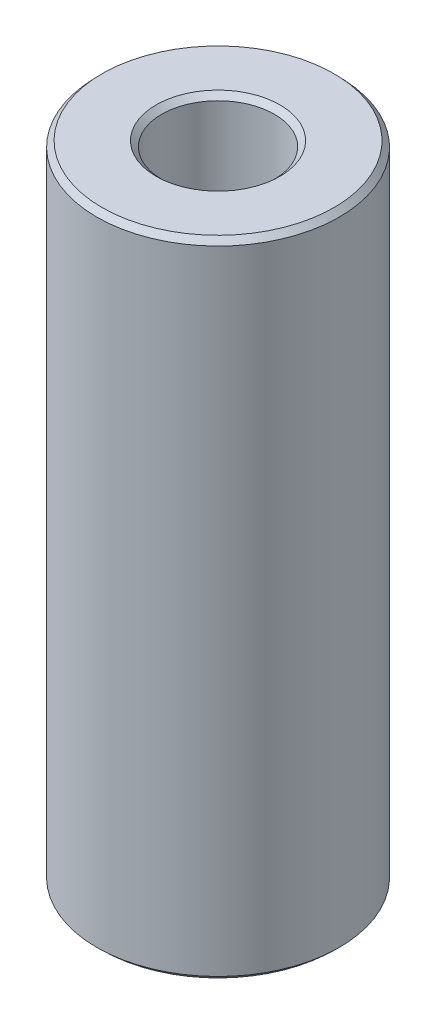
SolidWorks part; units mm, degrees
ref_plane "Front Plane" through (0, 0, 0) normal (0, 0, 1) x (1, 0, 0)
ref_plane "Top Plane" through (0, 0, 0) normal (0, 1, 0) x (1, 0, 0)
ref_plane "Right Plane" through (0, 0, 0) normal (1, 0, 0) x (0, 0, -1)
sketch "Sketch1" plane through (0, 0, 0) normal (0, 1, 0) x (1, 0, 0)
  circle A0 centre (0, 0) radius 60
  dimension "SLEEVE_OD" = 120
extrude "Boss-Extrude1" add sketch "Sketch1" along normal blind 318.3871
sketch "Sketch2" plane through (0, 0, 0) normal (0, 1, 0) x (1, 0, 0)
  circle A0 centre (0, 0) radius 27.8797
  dimension "BORE_D" = 55.7593
extrude "Cut-Extrude1" cut sketch "Sketch2" along normal through all
chamfer "Chamfer1" distance 2.7775 angle 43.295 4 edges at (0, 318.3871, 27.8797) (0, 0, 27.8797) (0, 0, 60) (0, 318.3871, 60) first distance on face at (0, 318.3871, 27.8797) first distance on face at (0, 0, 27.8797) first distance on face at (0, 318.3871, 60)
